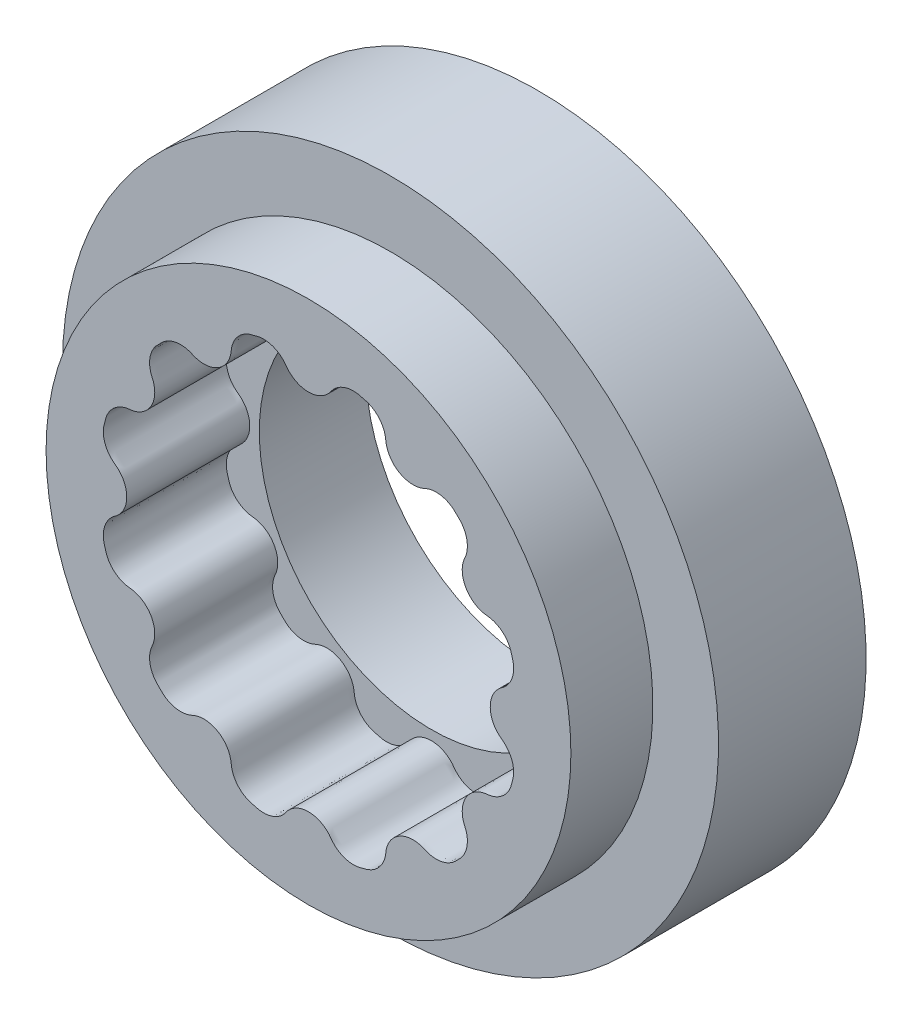
SolidWorks part; units mm, degrees
material "ABS PC"
ref_plane "Front Plane" through (0, 0, 0) normal (0, 0, 1) x (1, 0, 0)
ref_plane "Top Plane" through (0, 0, 0) normal (0, 1, 0) x (1, 0, 0)
ref_plane "Right Plane" through (0, 0, 0) normal (1, 0, 0) x (0, 0, -1)
sketch "Sketch1" plane through (0, 0, 0) normal (0, 0, 1) x (1, 0, 0)
  circle A2 centre (0, 0) radius 32
  spline S1 degree 3 poles (7.0087, -24.7259) (8.3877, -24.335) (9.3004, -23.23) (9.424, -21.8021) (9.424, -21.8014) (9.4241, -21.8) (9.4243, -21.798) (9.4244, -21.7967) (9.4245, -21.796) (9.6443, -19.2549) (11.8531, -17.9797) (14.1636, -19.0598) (14.1643, -19.0601) (14.1655, -19.0607) (14.1673, -19.0616) (14.1686, -19.0621) (14.1692, -19.0624) (15.4522, -19.6623) (16.8504, -19.4359) (17.8785, -18.4617) (17.8853, -18.4553) (17.8988, -18.4425) (17.9188, -18.423) (17.9322, -18.41) (17.9388, -18.4035) (18.0957, -18.2506) (18.2506, -18.0957) (18.4035, -17.9388) (18.41, -17.9322) (18.423, -17.9188) (18.4425, -17.8988) (18.4553, -17.8853) (18.4617, -17.8785) (19.4359, -16.8504) (19.6623, -15.4522) (19.0624, -14.1692) (19.0621, -14.1686) (19.0616, -14.1673) (19.0607, -14.1655) (19.0601, -14.1643) (19.0598, -14.1636) (17.9797, -11.8531) (19.2549, -9.6443) (21.796, -9.4245) (21.7967, -9.4244) (21.798, -9.4243) (21.8, -9.4241) (21.8014, -9.424) (21.8021, -9.424) (23.2132, -9.3019) (24.3108, -8.4068) (24.7141, -7.0491) (24.7168, -7.0401) (24.722, -7.0223) (24.7296, -6.9954) (24.7347, -6.9774) (24.7372, -6.9685) (24.7966, -6.7576) (24.8533, -6.546) (24.9073, -6.3337) (24.9096, -6.3247) (24.9142, -6.3067) (24.921, -6.2796) (24.9254, -6.2615) (24.9276, -6.2524) (25.2571, -4.8749) (24.7541, -3.5509) (23.5931, -2.7397) (23.5926, -2.7393) (23.5915, -2.7385) (23.5898, -2.7373) (23.5887, -2.7365) (23.5881, -2.7362) (21.4974, -1.2753) (21.4974, 1.2753) (23.5881, 2.7362) (23.5887, 2.7365) (23.5898, 2.7373) (23.5915, 2.7385) (23.5926, 2.7393) (23.5931, 2.7397) (24.7541, 3.5509) (25.2571, 4.8749) (24.9276, 6.2524) (24.9254, 6.2615) (24.921, 6.2796) (24.9142, 6.3067) (24.9096, 6.3247) (24.9073, 6.3337) (24.8533, 6.546) (24.7966, 6.7576) (24.7372, 6.9685) (24.7347, 6.9774) (24.7296, 6.9954) (24.722, 7.0223) (24.7168, 7.0401) (24.7141, 7.0491) (24.3108, 8.4068) (23.2132, 9.3019) (21.8021, 9.424) (21.8014, 9.424) (21.8, 9.4241) (21.798, 9.4243) (21.7967, 9.4244) (21.796, 9.4245) (19.2549, 9.6443) (17.9797, 11.8531) (19.0598, 14.1636) (19.0601, 14.1643) (19.0607, 14.1655) (19.0616, 14.1673) (19.0621, 14.1686) (19.0624, 14.1692) (19.6623, 15.4522) (19.4359, 16.8504) (18.4617, 17.8785) (18.4553, 17.8853) (18.4425, 17.8988) (18.423, 17.9188) (18.41, 17.9322) (18.4035, 17.9388) (18.2506, 18.0957) (18.0957, 18.2506) (17.9388, 18.4035) (17.9322, 18.41) (17.9188, 18.423) (17.8988, 18.4425) (17.8853, 18.4553) (17.8785, 18.4617) (16.8504, 19.4359) (15.4522, 19.6623) (14.1692, 19.0624) (14.1686, 19.0621) (14.1673, 19.0616) (14.1655, 19.0607) (14.1643, 19.0601) (14.1636, 19.0598) (11.8531, 17.9797) (9.6443, 19.2549) (9.4245, 21.796) (9.4244, 21.7967) (9.4243, 21.798) (9.4241, 21.8) (9.424, 21.8014) (9.424, 21.8021) (9.3019, 23.2132) (8.4068, 24.3108) (7.0491, 24.7141) (7.0401, 24.7168) (7.0223, 24.722) (6.9954, 24.7296) (6.9774, 24.7347) (6.9685, 24.7372) (6.7576, 24.7966) (6.546, 24.8533) (6.3337, 24.9073) (6.3247, 24.9096) (6.3067, 24.9142) (6.2796, 24.921) (6.2615, 24.9254) (6.2524, 24.9276) (4.8749, 25.2571) (3.5509, 24.7541) (2.7397, 23.5931) (2.7393, 23.5926) (2.7385, 23.5915) (2.7373, 23.5898) (2.7365, 23.5887) (2.7362, 23.5881) (1.2753, 21.4974) (-1.2753, 21.4974) (-2.7362, 23.5881) (-2.7365, 23.5887) (-2.7373, 23.5898) (-2.7385, 23.5915) (-2.7393, 23.5926) (-2.7397, 23.5931) (-3.5509, 24.7541) (-4.8749, 25.2571) (-6.2524, 24.9276) (-6.2615, 24.9254) (-6.2796, 24.921) (-6.3067, 24.9142) (-6.3247, 24.9096) (-6.3337, 24.9073) (-6.546, 24.8533) (-6.7576, 24.7966) (-6.9685, 24.7372) (-6.9774, 24.7347) (-6.9954, 24.7296) (-7.0223, 24.722) (-7.0401, 24.7168) (-7.0491, 24.7141) (-8.4068, 24.3108) (-9.3019, 23.2132) (-9.424, 21.8021) (-9.424, 21.8014) (-9.4241, 21.8) (-9.4243, 21.798) (-9.4244, 21.7967) (-9.4245, 21.796) (-9.6443, 19.2549) (-11.8531, 17.9797) (-14.1636, 19.0598) (-14.1643, 19.0601) (-14.1655, 19.0607) (-14.1673, 19.0616) (-14.1686, 19.0621) (-14.1692, 19.0624) (-15.4522, 19.6623) (-16.8504, 19.4359) (-17.8785, 18.4617) (-17.8853, 18.4553) (-17.8988, 18.4425) (-17.9188, 18.423) (-17.9322, 18.41) (-17.9388, 18.4035) (-18.0957, 18.2506) (-18.2506, 18.0957) (-18.4035, 17.9388) (-18.41, 17.9322) (-18.423, 17.9188) (-18.4425, 17.8988) (-18.4553, 17.8853) (-18.4617, 17.8785) (-19.4359, 16.8504) (-19.6623, 15.4522) (-19.0624, 14.1692) (-19.0621, 14.1686) (-19.0616, 14.1673) (-19.0607, 14.1655) (-19.0601, 14.1643) (-19.0598, 14.1636) (-17.9797, 11.8531) (-19.2549, 9.6443) (-21.796, 9.4245) (-21.7967, 9.4244) (-21.798, 9.4243) (-21.8, 9.4241) (-21.8014, 9.424) (-21.8021, 9.424) (-23.2132, 9.3019) (-24.3108, 8.4068) (-24.7141, 7.0491) (-24.7168, 7.0401) (-24.722, 7.0223) (-24.7296, 6.9954) (-24.7347, 6.9774) (-24.7372, 6.9685) (-24.7966, 6.7576) (-24.8533, 6.546) (-24.9073, 6.3337) (-24.9096, 6.3247) (-24.9142, 6.3067) (-24.921, 6.2796) (-24.9254, 6.2615) (-24.9276, 6.2524) (-25.2571, 4.8749) (-24.7541, 3.5509) (-23.5931, 2.7397) (-23.5926, 2.7393) (-23.5915, 2.7385) (-23.5898, 2.7373) (-23.5887, 2.7365) (-23.5881, 2.7362) (-21.4974, 1.2753) (-21.4974, -1.2753) (-23.5881, -2.7362) (-23.5887, -2.7365) (-23.5898, -2.7373) (-23.5915, -2.7385) (-23.5926, -2.7393) (-23.5931, -2.7397) (-24.7541, -3.5509) (-25.2571, -4.8749) (-24.9276, -6.2524) (-24.9254, -6.2615) (-24.921, -6.2796) (-24.9142, -6.3067) (-24.9096, -6.3247) (-24.9073, -6.3337) (-24.8533, -6.546) (-24.7966, -6.7576) (-24.7372, -6.9685) (-24.7347, -6.9774) (-24.7296, -6.9954) (-24.722, -7.0223) (-24.7168, -7.0401) (-24.7141, -7.0491) (-24.3108, -8.4068) (-23.2132, -9.3019) (-21.8021, -9.424) (-21.8014, -9.424) (-21.8, -9.4241) (-21.798, -9.4243) (-21.7967, -9.4244) (-21.796, -9.4245) (-19.2549, -9.6443) (-17.9797, -11.8531) (-19.0598, -14.1636) (-19.0601, -14.1643) (-19.0607, -14.1655) (-19.0616, -14.1673) (-19.0621, -14.1686) (-19.0624, -14.1692) (-19.6623, -15.4522) (-19.4359, -16.8504) (-18.4617, -17.8785) (-18.4553, -17.8853) (-18.4425, -17.8988) (-18.423, -17.9188) (-18.41, -17.9322) (-18.4035, -17.9388) (-18.2506, -18.0957) (-18.0957, -18.2506) (-17.9388, -18.4035) (-17.9322, -18.41) (-17.9188, -18.423) (-17.8988, -18.4425) (-17.8853, -18.4553) (-17.8785, -18.4617) (-16.8504, -19.4359) (-15.4522, -19.6623) (-14.1692, -19.0624) (-14.1686, -19.0621) (-14.1673, -19.0616) (-14.1655, -19.0607) (-14.1643, -19.0601) (-14.1636, -19.0598) (-11.8531, -17.9797) (-9.6443, -19.2549) (-9.4245, -21.796) (-9.4244, -21.7967) (-9.4243, -21.798) (-9.4241, -21.8) (-9.424, -21.8014) (-9.424, -21.8021) (-9.3019, -23.2132) (-8.4068, -24.3108) (-7.0491, -24.7141) (-7.0401, -24.7168) (-7.0223, -24.722) (-6.9954, -24.7296) (-6.9774, -24.7347) (-6.9685, -24.7372) (-6.7576, -24.7966) (-6.546, -24.8533) (-6.3337, -24.9073) (-6.3247, -24.9096) (-6.3067, -24.9142) (-6.2796, -24.921) (-6.2615, -24.9254) (-6.2524, -24.9276) (-4.8749, -25.2571) (-3.5509, -24.7541) (-2.7397, -23.5931) (-2.7393, -23.5926) (-2.7385, -23.5915) (-2.7373, -23.5898) (-2.7365, -23.5887) (-2.7362, -23.5881) (-1.2753, -21.4974) (1.2753, -21.4974) (2.7362, -23.5881) (2.7365, -23.5887) (2.7373, -23.5898) (2.7385, -23.5915) (2.7393, -23.5926) (2.7397, -23.5931) (3.5606, -24.768) (4.9036, -25.2685) (6.2932, -24.9176) (6.373, -24.8974) (6.5311, -24.8512) (6.7695, -24.7873) (6.9295, -24.7483) (7.0087, -24.7259) (8.3877, -24.335) (9.3004, -23.23) knots -0.001489 0 0 0 0.022862 0.022862 0.022862 0.022874 0.022886 0.022898 0.022898 0.022898 0.055888 0.055888 0.055888 0.0559 0.055912 0.055925 0.055925 0.055925 0.078577 0.078577 0.078577 0.078746 0.078914 0.079083 0.079083 0.079083 0.083044 0.083044 0.083044 0.083213 0.083381 0.08355 0.08355 0.08355 0.106202 0.106202 0.106202 0.106215 0.106227 0.106239 0.106239 0.106239 0.139228 0.139228 0.139228 0.139241 0.139253 0.139265 0.139265 0.139265 0.161918 0.161918 0.161918 0.162087 0.162255 0.162424 0.162424 0.162424 0.166385 0.166385 0.166385 0.166553 0.166722 0.16689 0.16689 0.16689 0.189543 0.189543 0.189543 0.189555 0.189568 0.18958 0.18958 0.18958 0.222569 0.222569 0.222569 0.222581 0.222594 0.222606 0.222606 0.222606 0.245259 0.245259 0.245259 0.245427 0.245596 0.245764 0.245764 0.245764 0.249726 0.249726 0.249726 0.249894 0.250063 0.250231 0.250231 0.250231 0.272884 0.272884 0.272884 0.272896 0.272908 0.272921 0.272921 0.272921 0.30591 0.30591 0.30591 0.305922 0.305935 0.305947 0.305947 0.305947 0.3286 0.3286 0.3286 0.328768 0.328937 0.329105 0.329105 0.329105 0.333066 0.333066 0.333066 0.333235 0.333403 0.333572 0.333572 0.333572 0.356225 0.356225 0.356225 0.356237 0.356249 0.356261 0.356261 0.356261 0.389251 0.389251 0.389251 0.389263 0.389275 0.389288 0.389288 0.389288 0.41194 0.41194 0.41194 0.412109 0.412277 0.412446 0.412446 0.412446 0.416407 0.416407 0.416407 0.416576 0.416744 0.416912 0.416912 0.416912 0.439565 0.439565 0.439565 0.439578 0.43959 0.439602 0.439602 0.439602 0.472591 0.472591 0.472591 0.472604 0.472616 0.472628 0.472628 0.472628 0.495281 0.495281 0.495281 0.49545 0.495618 0.495787 0.495787 0.495787 0.499748 0.499748 0.499748 0.499916 0.500085 0.500253 0.500253 0.500253 0.522906 0.522906 0.522906 0.522918 0.522931 0.522943 0.522943 0.522943 0.555932 0.555932 0.555932 0.555944 0.555957 0.555969 0.555969 0.555969 0.578622 0.578622 0.578622 0.57879 0.578959 0.579127 0.579127 0.579127 0.583089 0.583089 0.583089 0.583257 0.583425 0.583594 0.583594 0.583594 0.606247 0.606247 0.606247 0.606259 0.606271 0.606284 0.606284 0.606284 0.639273 0.639273 0.639273 0.639285 0.639297 0.63931 0.63931 0.63931 0.661963 0.661963 0.661963 0.662131 0.662299 0.662468 0.662468 0.662468 0.666429 0.666429 0.666429 0.666598 0.666766 0.666935 0.666935 0.666935 0.689588 0.689588 0.689588 0.6896 0.689612 0.689624 0.689624 0.689624 0.722614 0.722614 0.722614 0.722626 0.722638 0.72265 0.72265 0.72265 0.745303 0.745303 0.745303 0.745472 0.74564 0.745809 0.745809 0.745809 0.74977 0.74977 0.74977 0.749938 0.750107 0.750275 0.750275 0.750275 0.772928 0.772928 0.772928 0.772941 0.772953 0.772965 0.772965 0.772965 0.805954 0.805954 0.805954 0.805967 0.805979 0.805991 0.805991 0.805991 0.828644 0.828644 0.828644 0.828812 0.828981 0.829149 0.829149 0.829149 0.833111 0.833111 0.833111 0.833279 0.833448 0.833616 0.833616 0.833616 0.856269 0.856269 0.856269 0.856281 0.856294 0.856306 0.856306 0.856306 0.889295 0.889295 0.889295 0.889307 0.88932 0.889332 0.889332 0.889332 0.911985 0.911985 0.911985 0.912153 0.912322 0.91249 0.91249 0.91249 0.916451 0.916451 0.916451 0.91662 0.916788 0.916957 0.916957 0.916957 0.93961 0.93961 0.93961 0.939622 0.939634 0.939647 0.939647 0.939647 0.972636 0.972636 0.972636 0.972648 0.97266 0.972673 0.972673 0.972673 0.995534 0.995534 0.995534 0.997023 0.998511 1 1 1 1.022862 1.022862 1.022862 weights 1 0.881989 0.881989 1 1 1 1 1 1 0.715182 0.715182 1 1 1 1 1 1 0.884361 0.884361 1 1 1 1 1 1 0.999946 0.999946 1 1 1 1 1 1 0.884361 0.884361 1 1 1 1 1 1 0.715182 0.715182 1 1 1 1 1 1 0.884361 0.884361 1 1 1 1 1 1 0.999946 0.999946 1 1 1 1 1 1 0.884361 0.884361 1 1 1 1 1 1 0.715182 0.715182 1 1 1 1 1 1 0.884361 0.884361 1 1 1 1 1 1 0.999946 0.999946 1 1 1 1 1 1 0.884361 0.884361 1 1 1 1 1 1 0.715182 0.715182 1 1 1 1 1 1 0.884361 0.884361 1 1 1 1 1 1 0.999946 0.999946 1 1 1 1 1 1 0.884361 0.884361 1 1 1 1 1 1 0.715182 0.715182 1 1 1 1 1 1 0.884361 0.884361 1 1 1 1 1 1 0.999946 0.999946 1 1 1 1 1 1 0.884361 0.884361 1 1 1 1 1 1 0.715182 0.715182 1 1 1 1 1 1 0.884361 0.884361 1 1 1 1 1 1 0.999946 0.999946 1 1 1 1 1 1 0.884361 0.884361 1 1 1 1 1 1 0.715182 0.715182 1 1 1 1 1 1 0.884361 0.884361 1 1 1 1 1 1 0.999946 0.999946 1 1 1 1 1 1 0.884361 0.884361 1 1 1 1 1 1 0.715182 0.715182 1 1 1 1 1 1 0.884361 0.884361 1 1 1 1 1 1 0.999946 0.999946 1 1 1 1 1 1 0.884361 0.884361 1 1 1 1 1 1 0.715182 0.715182 1 1 1 1 1 1 0.884361 0.884361 1 1 1 1 1 1 0.999946 0.999946 1 1 1 1 1 1 0.884361 0.884361 1 1 1 1 1 1 0.715182 0.715182 1 1 1 1 1 1 0.884361 0.884361 1 1 1 1 1 1 0.999946 0.999946 1 1 1 1 1 1 0.884361 0.884361 1 1 1 1 1 1 0.715182 0.715182 1 1 1 1 1 1 0.884361 0.884361 1 1 1 1 1 1 0.999946 0.999946 1 1 1 1 1 1 0.884361 0.884361 1 1 1 1 1 1 0.715182 0.715182 1 1 1 1 1 1 0.881989 0.881989 1 1 1 1 1 1 0.881989 0.881989 only from (7.0087, -24.7259) to (7.0087, -24.7259)
  point P1 (0, 0)
  dimension "D1" = 64
extrude "Boss-Extrude1" add sketch "Sketch1" along normal blind 15
sketch "Sketch3" plane through (0, 0, 0) normal (0, 0, -1) x (-1, 0, 0)
  circle A0 centre (0, 0) radius 30
  circle A1 centre (0, 0) radius 40
  dimension "D1" = 80
extrude "Boss-Extrude3" add sketch "Sketch3" against normal blind 5
sketch "Sketch4" plane through (0, 0, 0) normal (0, 0, -1) x (-1, 0, 0)
  circle A0 centre (0, 0) radius 40
  circle A1 centre (0, 0) radius 21
  point P5 (0, 0)
  dimension "D1" = 42
extrude "Boss-Extrude4" add sketch "Sketch4" along normal blind 13
sketch "Sketch5" plane through (0, 0, -13) normal (0, 0, -1) x (-1, 0, 0)
  circle A0 centre (0, 35) radius 1.5
  circle A1 centre (24.7487, 24.7487) radius 1.5
  circle A2 centre (35, 0) radius 1.5
  circle A3 centre (24.7487, -24.7487) radius 1.5
  circle A4 centre (0, -35) radius 1.5
  circle A5 centre (-24.7487, -24.7487) radius 1.5
  circle A6 centre (-35, 0) radius 1.5
  circle A7 centre (-24.7487, 24.7487) radius 1.5
  point P19 (0, 0)
  dimension "D2" = 3
  dimension "D1" = 35
  dimension "D3" = 8
extrude "Cut-Extrude1" cut sketch "Sketch5" against normal blind 15
sketch "Sketch6" plane through (0, 0, -13) normal (0, 0, -1) x (-1, 0, 0)
  circle A0 centre (0, 35) radius 2.5
  circle A1 centre (35, 0) radius 2.5
  circle A2 centre (0, -35) radius 2.5
  circle A3 centre (-35, 0) radius 2.5
  point P12 (0, 0)
  dimension "D1" = 5
  dimension "D2" = 4
extrude "Cut-Extrude2" cut sketch "Sketch6" against normal blind 3
